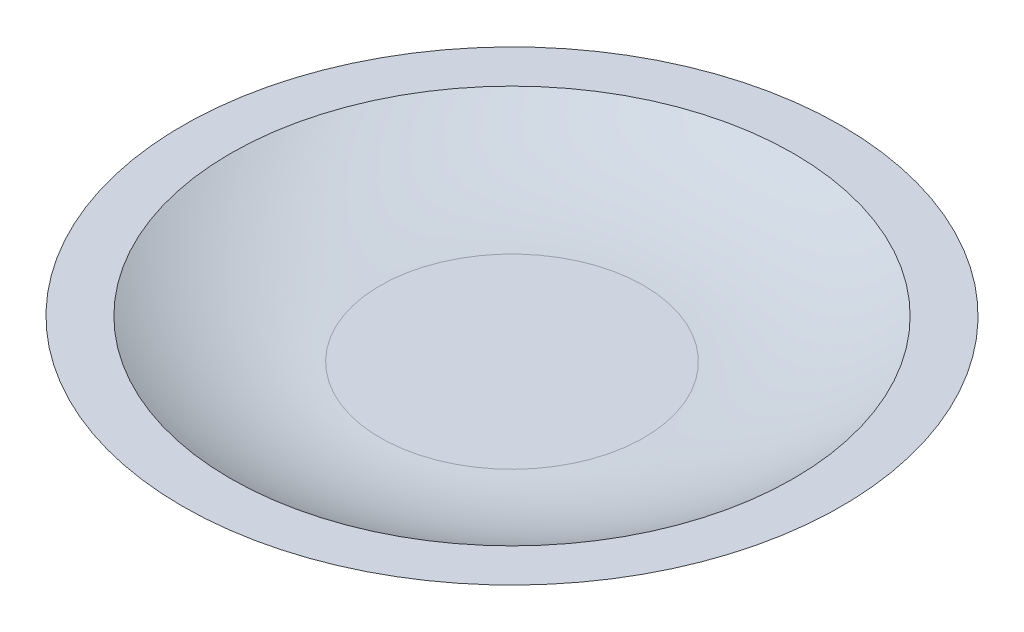
SolidWorks part; units mm, degrees
material "Titanium Ti-8Mn, Annealed"
ref_plane "Front Plane" through (0, 0, 0) normal (0, 0, 1) x (1, 0, 0)
ref_plane "Top Plane" through (0, 0, 0) normal (0, 1, 0) x (1, 0, 0)
ref_plane "Right Plane" through (0, 0, 0) normal (1, 0, 0) x (0, 0, -1)
sketch "Sketch1" plane through (0, 0, 0) normal (0, 1, 0) x (1, 0, 0)
  circle A0 centre (0, 0) radius 2500
  dimension "D1" = 5000
extrude "Boss-Extrude1" add sketch "Sketch1" against normal blind 500 contours A0
fillet "Fillet1" radius 2500 1 edges at (0, -500, 2500)
shell "Shell1" thickness 200 removed face at (0, 0, 2500)
